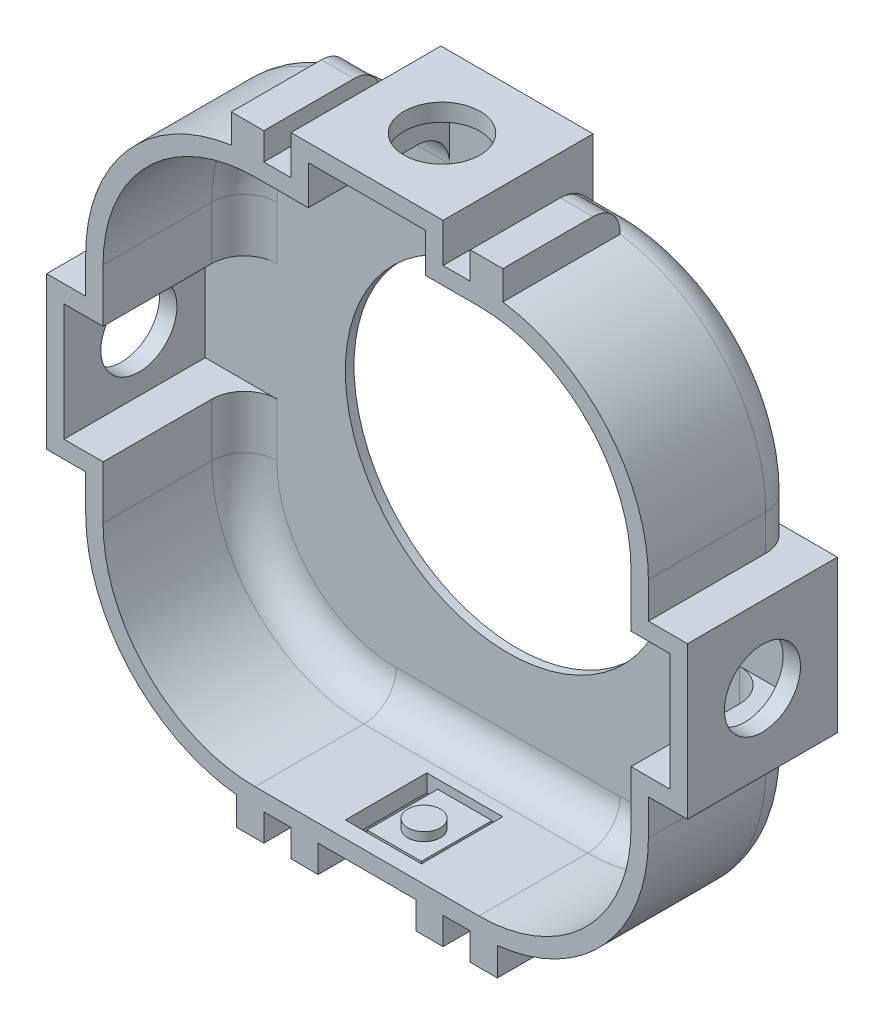
SolidWorks part; units mm, degrees
ref_plane "Спереди" through (0, 0, 0) normal (0, 0, 1) x (1, 0, 0)
ref_plane "Сверху" through (0, 0, 0) normal (0, 1, 0) x (1, 0, 0)
ref_plane "Справа" through (0, 0, 0) normal (1, 0, 0) x (0, 0, -1)
sketch "Эскиз-База" plane through (0, 0, 0) normal (0, 0, 1) x (1, 0, 0)
  line L0 (29.5, 0) -> (-29.5, 0) construction
  line L1 (-25.9, 25.9) -> (25.9, 25.9) construction
  line L2 (-25.9, 25.9) -> (-25.9, -25.9) construction
  line L3 (-25.9, -25.9) -> (25.9, -25.9) construction
  line L4 (25.9, 25.9) -> (25.9, -25.9) construction
  line L5 (-25.9, 25.9) -> (25.9, -25.9) construction
  line L6 (-25.9, -25.9) -> (25.9, 25.9) construction
  line L7 (0, -25.9) -> (0, 29.5) construction
  line L8 (-25.9, 7) -> (-29.5, 7)
  line L9 (-29.5, 7) -> (-29.5, -7)
  line L10 (-29.5, -7) -> (-25.9, -7)
  line L11 (25.9, 7) -> (29.5, 7)
  line L12 (29.5, 7) -> (29.5, -7)
  line L13 (29.5, -7) -> (25.9, -7)
  line L14 (-25.9, 10.3) -> (-25.9, 7)
  line L15 (-25.9, -10.3) -> (-25.9, -7)
  line L16 (-10.3, -25.9) -> (10.3, -25.9)
  line L17 (25.9, -10.3) -> (25.9, -7)
  line L18 (25.9, 7) -> (25.9, 10.3)
  line L19 (-7, 25.9) -> (-7, 29.5)
  line L20 (-7, 29.5) -> (7, 29.5)
  line L21 (7, 29.5) -> (7, 25.9)
  line L25 (-10.3, 25.9) -> (-7, 25.9)
  line L26 (7, 25.9) -> (10.3, 25.9)
  arc A0 (-25.9, 10.3) -> (-10.3, 25.9) centre (-10.3, 10.3) cw
  arc A1 (25.9, 10.3) -> (10.3, 25.9) centre (10.3, 10.3) ccw
  arc A2 (25.9, -10.3) -> (10.3, -25.9) centre (10.3, -10.3) cw
  arc A3 (-25.9, -10.3) -> (-10.3, -25.9) centre (-10.3, -10.3) ccw
  circle A4 centre (0, 0) radius 15
  point P0 (0, 0)
  point P17 (-29.5, 0)
  point P24 (29.5, 0)
  point P36 (0, 29.5)
  dimension "D2" = 15.6
  dimension "D3" = 15.6
  dimension "D5" = 59
  dimension "D6" = 14
  dimension "D8" = 30
  dimension "D1" = 51.8
  dimension "D4" = 14
  dimension "D7" = 29.5
extrude "Вытянуть-Стенки" add sketch "Эскиз-База" along normal blind 13 from surface thin contours A0 L25 L19 L20 L21 L26 A1 L18 L11 L12 L13 L17 A2 L16 A3 L15 L10 L9 L8 L14 starting at plane "Спереди" thin type one direction reverse wall 1.6
extrude "Бобышка-Дно" add sketch "Эскиз-База<8>" against normal blind 0.8
sketch "Эскиз-База<8>" plane through (0, 0, 0) normal (0, 0, 1) x (1, 0, 0) same geometry as "Эскиз-База"
sketch "Эскиз-Левое отверстие" plane through (-29.5, 0, 0) normal (-1, 0, 0) x (0, 0, 1)
  line L0 (-0.8, 7) -> (13, -7) construction
  line L1 (-0.8, -7) -> (13, 7) construction
  circle A0 centre (6.1, 0) radius 3.5
  dimension "D1" = 7
extrude "Вырез-Отверстия слева справа" cut sketch "Эскиз-Левое отверстие" against normal up to surface (59 mm away)
sketch "Эскиз-Отверстие сверху" plane through (0, 29.5, 0) normal (0, 1, 0) x (1, 0, 0)
  line L0 (-7, 0.8) -> (7, -13) construction
  line L1 (-7, -13) -> (7, 0.8) construction
  circle A0 centre (0, -6.1) radius 3.5
  dimension "D1" = 7
extrude "Вырез-Верхнее отверстие" cut sketch "Эскиз-Отверстие сверху" against normal up to next
sketch "Эскиз-Кнопка записи" plane through (0, -25.9, 0) normal (0, -1, 0) x (1, 0, 0)
  line L0 (-10.3, 7.75) -> (10.3, 7.75) construction
  line L1 (-10.3, 13) -> (-10.3, -0.8) construction
  line L2 (10.3, 13) -> (10.3, -0.8) construction
  line L3 (50, 0) -> (-50, 0) construction
  line L4 (0, 13) -> (0, -0.8) construction
  line L5 (-10.3, 13) -> (10.3, 13) construction
  line L6 (-10.3, -0.8) -> (10.3, -0.8) construction
  line L7 (-2.5, 4) -> (-2.5, 10.5)
  line L8 (-2.5, 10.5) -> (2.5, 10.5)
  line L9 (3.5, 4) -> (2.5, 4)
  line L10 (3.5, 11.5) -> (-3.5, 11.5)
  line L11 (-3.5, 11.5) -> (-3.5, 4)
  line L12 (-3.5, 4) -> (-2.5, 4)
  line L13 (2.5, 4) -> (2.5, 10.5)
  line L14 (3.5, 11.5) -> (3.5, 4)
  line L15 (-2.5, 4) -> (2.5, 4)
  line L16 (-2.5, 4) -> (-2.5, 2.25)
  line L17 (-2.5, 2.25) -> (2.5, 2.25)
  line L18 (2.5, 2.25) -> (2.5, 4)
  circle A0 centre (0, 7.75) radius 1.5
  point P25 (0, 10.5)
  point P26 (0, 11.5)
  dimension "D2" = 3
  dimension "D1" = 7.75
  dimension "D3" = 1
  dimension "D4" = 1
  dimension "D5" = 4
  dimension "D6" = 11.5
  dimension "D7" = 3.5
  dimension "D8" = 1.75
extrude "Вырез-Рамка кнопки" cut sketch "Эскиз-Кнопка записи" against normal up to next contours L14 L10 L11 L12 L7 L8 L13 L9 region at (-3, -25.9, 4.1026)
extrude "Вырез-Утоньшение кнопки" cut sketch "Эскиз-Кнопка записи<3>" against normal up to next from offset 0.8 contours L7 L15 L13 L8 A0 region at (-2.418, -25.9, 7.25) offset against normal yes
sketch "Эскиз-Кнопка записи<3>" plane through (0, -25.9, 0) normal (0, -1, 0) x (1, 0, 0) same geometry as "Эскиз-Кнопка записи"
fillet "Скругление-Внутреннее" radius 3 11 edges at (-24.3, -7.85, 0) (24.3, -7.85, 0) (20.1995, -20.1995, 0) (0, -24.3, 0) (24.3, 7.85, 0) (7.85, 24.3, 0) (-7.85, 24.3, 0) (-24.3, 7.85, 0) (-20.1995, -20.1995, 0) (20.1995, 20.1995, 0) (-20.1995, 20.1995, 0)
fillet "Скругление-Наружное" radius 3 11 edges at (-25.9, 8.65, -0.8) (-25.9, -8.65, -0.8) (-21.3309, -21.3309, -0.8) (0, -25.9, -0.8) (21.3309, -21.3309, -0.8) (25.9, -8.65, -0.8) (25.9, 8.65, -0.8) (21.3309, 21.3309, -0.8) (8.65, 25.9, -0.8) (-8.65, 25.9, -0.8) (-21.3309, 21.3309, -0.8)
sketch "Эскиз-Фиксатор резинки" plane through (0, 0, 0) normal (0, 0, 1) x (1, 0, 0)
  line L0 (-9.5, 25.9) -> (-9.5, 28.4)
  line L1 (-7, 25.9) -> (-10.3, 25.9) construction
  line L2 (-9.5, 28.4) -> (-12.5, 28.4)
  line L3 (-12.5, 28.4) -> (-12.5, 25.4)
  line L4 (12, -25.4) -> (9.5, -25.9)
  line L5 (-7, 29.5) -> (-7, 25.9) construction
  line L6 (0, 29.5) -> (0, -25.9) construction
  line L7 (7, 29.5) -> (-7, 29.5) construction
  line L8 (10.3, -25.9) -> (-10.3, -25.9) construction
  line L9 (9.5, 25.9) -> (9.5, 28.4)
  line L10 (9.5, 28.4) -> (12.5, 28.4)
  line L11 (12.5, 25.4) -> (9.5, 25.9)
  line L12 (-9.5, -25.9) -> (-9.5, -28.4)
  line L13 (-9.5, -28.4) -> (-12, -28.4)
  line L14 (-12, -28.4) -> (-12, -25.4)
  line L15 (9.5, -28.4) -> (12, -28.4)
  line L16 (9.5, -25.9) -> (9.5, -28.4)
  line L17 (-12, -25.4) -> (-9.5, -25.9)
  line L18 (12, -28.4) -> (12, -25.4)
  line L19 (-12.5, 25.4) -> (-9.5, 25.9)
  line L20 (12.5, 28.4) -> (12.5, 25.4)
  line L21 (-7, -25.9) -> (-7, -28.4)
  line L22 (-7, -28.4) -> (-4.5, -28.4)
  line L23 (-4.5, -28.4) -> (-4.5, -25.9)
  line L24 (-7, -25.9) -> (-4.5, -25.9)
  line L25 (4.5, -28.4) -> (4.5, -25.9)
  line L26 (7, -28.4) -> (4.5, -28.4)
  line L27 (7, -25.9) -> (7, -28.4)
  line L28 (7, -25.9) -> (4.5, -25.9)
  dimension "D1" = 2.5
  dimension "D2" = 3
  dimension "D3" = 2.5
  dimension "D4" = 9.5
  dimension "D5" = 2.5
  dimension "D6" = 3
  dimension "D7" = 2.5
  dimension "D8" = 3
  dimension "D9" = 2.5
  dimension "D10" = 2.5
extrude "Бобышка-Фиксатор резинки" add sketch "Эскиз-Фиксатор резинки" along normal up to surface (13 mm away) from offset 2.2 up to face at (0, 5.54, 13)
extrude "Бобышка-Утолщение кнопки" add sketch "Эскиз-Кнопка записи<5>" along normal blind 2.5 contours L7 L15 L13 L8 A0 | A0 region at (-2.418, -25.9, 7.25) region at (0, -25.9, 7.75)
sketch "Эскиз-Кнопка записи<5>" plane through (0, -25.9, 0) normal (0, -1, 0) x (1, 0, 0) same geometry as "Эскиз-Кнопка записи"
fillet "Скругление1" radius 2.5 6 edges at (10.75, -28.4, 2.2) (5.75, -28.4, 2.2) (-10.75, -28.4, 2.2) (-5.75, -28.4, 2.2) (11, 28.4, 2.2) (-11, 28.4, 2.2)
chamfer "Фаска1" distance 2.5 angle 45 1 edges at (0, -28.4, 4)
